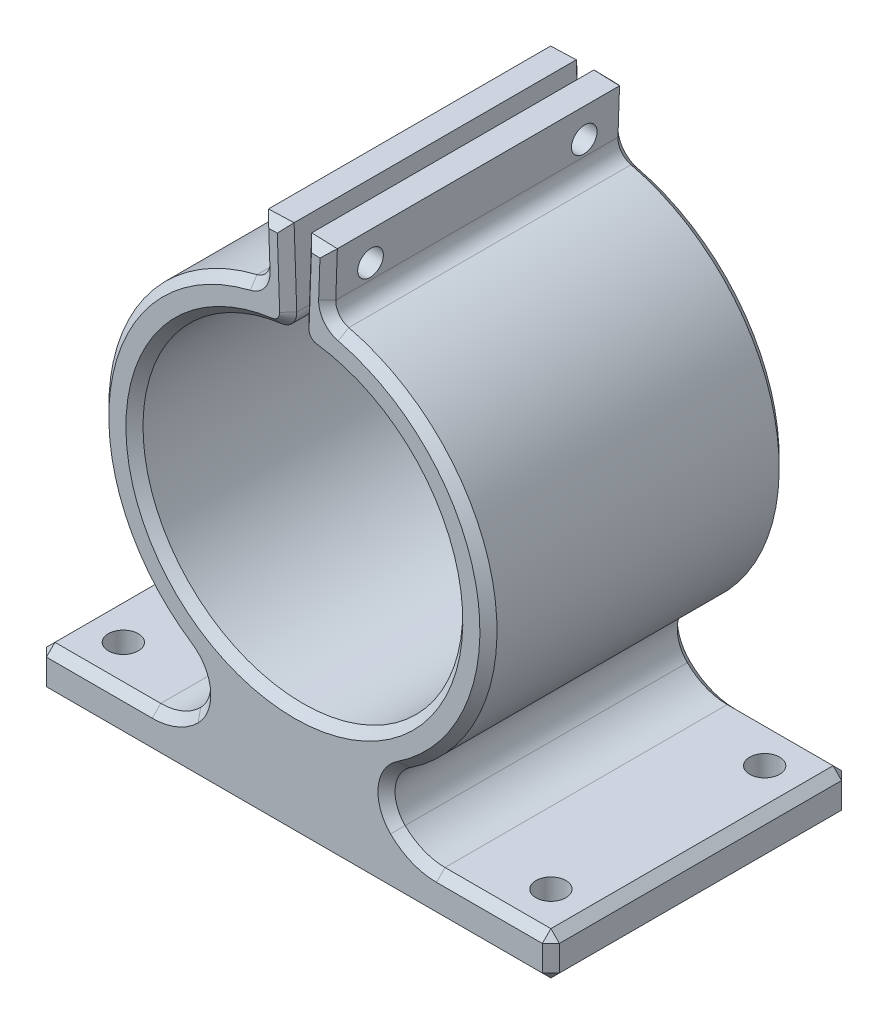
SolidWorks part; units mm, degrees
ref_plane "Front Plane" through (0, 0, 0) normal (0, 0, 1) x (1, 0, 0)
ref_plane "Top Plane" through (0, 0, 0) normal (0, 1, 0) x (1, 0, 0)
ref_plane "Right Plane" through (0, 0, 0) normal (1, 0, 0) x (0, 0, -1)
sketch "Sketch1" plane through (0, 0, 0) normal (0, 0, 1) x (1, 0, 0)
  line L0 (0, 0) -> (0, -32)
  line L1 (-30, -32) -> (30, -32)
  line L2 (30, -32) -> (30, -27)
  line L3 (0, 0) -> (0.7922, 22.6862)
  line L4 (30, -27) -> (16.6213, -27)
  line L5 (10, -20.3787) -> (10, -15.8016)
  line L6 (-30, -32) -> (-30, -27)
  line L7 (-30, -27) -> (-16.6213, -27)
  line L8 (-10, -20.3787) -> (-10, -15.8016)
  line L9 (0, 0) -> (-0.7922, 22.6862)
  line L10 (0.7922, 22.6862) -> (1.0296, 29.4829)
  line L11 (1.0296, 29.4829) -> (4.0277, 29.3782)
  line L12 (4.0277, 29.3782) -> (3.7834, 22.3825)
  line L13 (-0.7922, 22.6862) -> (-1.0296, 29.4829)
  line L14 (-1.0296, 29.4829) -> (-4.0277, 29.3782)
  line L15 (-4.0277, 29.3782) -> (-3.7834, 22.3825)
  arc A0 (-0.6526, 18.6886) -> (0.6526, 18.6886) centre (0, 0) ccw
  arc A1 (-0.7922, 22.6862) -> (0.7922, 22.6862) centre (0, 0) ccw
  arc A2 (16.6213, -27) -> (10, -20.3787) centre (16.6213, -20.3787) cw
  arc A3 (-16.6213, -27) -> (-10, -20.3787) centre (-16.6213, -20.3787) ccw
  dimension "D1" = 37.4
  dimension "D2" = 4
  dimension "D4" = 32
  dimension "D3" = 178
  dimension "D5" = 5
  dimension "D6" = 30
  dimension "D7" = 10
  dimension "D8" = 3
  dimension "D9" = 7
extrude "Boss-Extrude1" add sketch "Sketch1" along normal blind 35 contours L9 A1 L8 A0 | L8 A1 L0 A0 | L0 A1 L5 A0 | L5 A1 L3 A0 | L4 A2 A1 L0 L1 L2 | A3 L7 L6 L1 L0 A1 | A1 L13 L14 L15 | A1 L12 L11 L10 region at (5.1101, -19.8237, 0) region at (-5.1101, -19.8237, 0) region at (1.2059, 20.6705, 0) region at (-18.5159, 5.0181, 0) region at (12.5249, -28.0994, 0) region at (-12.5249, -28.0994, 0) region at (2.4161, 25.9986, 0) region at (-2.4161, 25.9986, 0)
sketch "Sketch2" plane through (0, 0, 0) normal (1, 0, 0) x (0, 0, -1)
  line L0 (-35, 29.3782) -> (-35, 22.3825) construction
  line L1 (-35, 29.3782) -> (-35, 22.3825)
  line L2 (-35, 25.8804) -> (0, 25.8804) construction
  line L3 (0, 29.3782) -> (0, 22.3825) construction
  circle A0 centre (-30, 25.8804) radius 1.5
  circle A1 centre (-5, 25.8804) radius 1.5
  dimension "D1" = 3
  dimension "D2" = 5
  dimension "D3" = 5
extrude "Cut-Extrude1" cut sketch "Sketch2" against normal through all both and the other way through all contours L2 A1 | L2 A0 | A0 L2 | A1 L2 region at (0, 26.517, 30) region at (0, 26.517, 5) region at (0, 25.2437, 5) region at (0, 25.2437, 30)
sketch "Sketch3" plane through (0, -27, 0) normal (0, 1, 0) x (1, 0, 0)
  line L8 (25, -5) -> (-25, -5)
  line L9 (25, -30) -> (25, -5)
  line L10 (-25, -30) -> (25, -30)
  line L11 (-25, -5) -> (-25, -30)
  line L12 (25, -5) -> (-25, -5) construction
  line L13 (25, -30) -> (25, -5) construction
  line L14 (-25, -30) -> (25, -30) construction
  line L15 (-25, -5) -> (-25, -30) construction
  circle A0 centre (-25, -5) radius 1.75
  circle A1 centre (-25, -30) radius 1.75
  circle A2 centre (25, -30) radius 1.75
  circle A3 centre (25, -5) radius 1.75
  dimension "D2" = 3.5
  dimension "D1" = 5
extrude "Cut-Extrude2" cut sketch "Sketch3" against normal through all
fillet "Fillet1" radius 4 2 edges at (-10, -20.3787, 17.5) (10, -20.3787, 17.5)
fillet "Fillet2" radius 2 4 edges at (3.7834, 22.3825, 17.5) (-0.6526, 18.6886, 17.5) (0.6526, 18.6886, 17.5) (-3.7834, 22.3825, 17.5)
chamfer "Chamfer1" distance 1 angle 45 48 edges at (30, -29.5, 0) (23.3107, -27, 0) (14.0993, -26.5009, 0) (3.935, 26.7237, 0) (2.5287, 29.4306, 0) (0.8743, 25.0368, 0) (0, -18.7, 0) (-0.8743, 25.0368, 0) (-2.5287, 29.4306, 0) (-3.935, 26.7237, 0) (-14.0993, -26.5009, 0) (-23.3107, -27, 0) (-30, -29.5, 0) (0, -32, 0) (-30, -29.5, 35) (-23.3107, -27, 35) (-14.0993, -26.5009, 35) (-3.935, 26.7237, 35) (-2.5287, 29.4306, 35) (-0.8743, 25.0368, 35) (0, -18.7, 35) (0.8743, 25.0368, 35) (2.5287, 29.4306, 35) (3.935, 26.7237, 35) (14.0993, -26.5009, 35) (23.3107, -27, 35) (30, -29.5, 35) (0, -32, 35) (-4.2472, 22.7913, 0) (-22.3579, 3.9261, 0) (-10.794, -21.8498, 0) (10.794, -21.8498, 0) (22.3579, 3.9261, 0) (4.2472, 22.7913, 0) (1.1909, 19.2291, 0) (-1.1909, 19.2291, 0) (1.1909, 19.2291, 35) (4.2472, 22.7913, 35) (22.3579, 3.9261, 35) (10.794, -21.8498, 35) (-10.794, -21.8498, 35) (-22.3579, 3.9261, 35) (-4.2472, 22.7913, 35) (-1.1909, 19.2291, 35) (-30, -27, 17.5) (-30, -32, 17.5) (30, -32, 17.5) (30, -27, 17.5)
